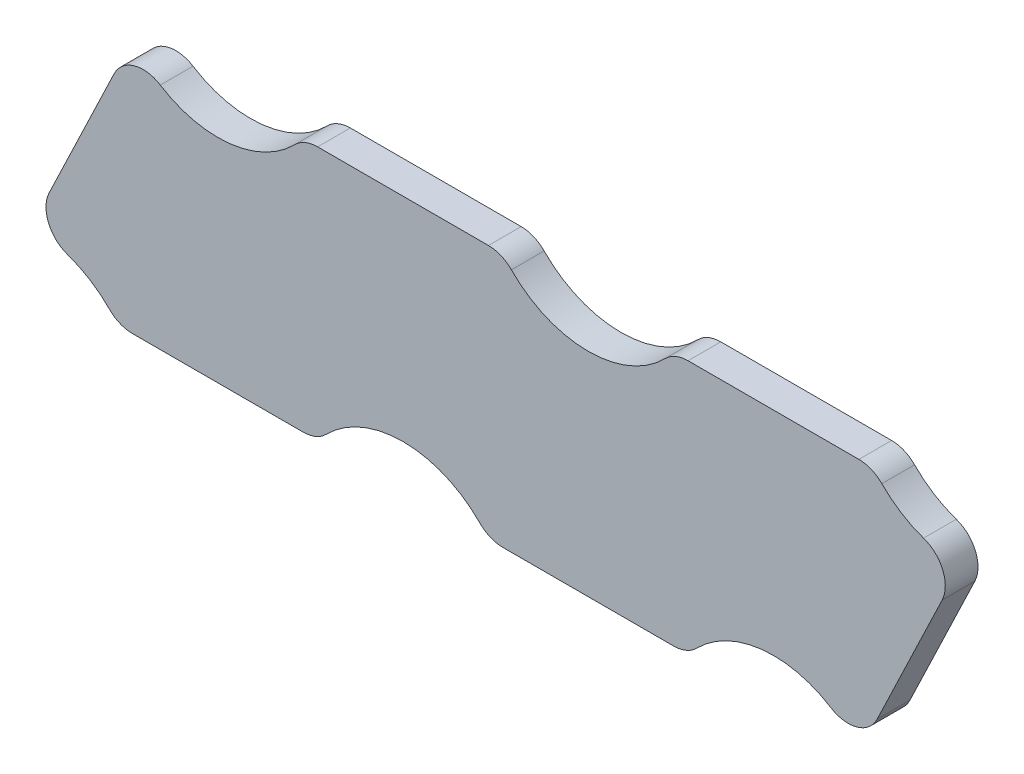
SolidWorks part; units mm, degrees
material "3003-H14"
ref_plane "X-Y Datum" through (0, 0, 0) normal (0, 0, 1) x (1, 0, 0)
ref_plane "X-Z Datum" through (0, 0, 0) normal (0, 1, 0) x (1, 0, 0)
ref_plane "Y-Z Datum" through (0, 0, 0) normal (1, 0, 0) x (0, 0, -1)
sketch "Sketch3" plane through (0, 0, 0) normal (0, 0, 1) x (1, 0, 0)
  line L0 (10.775, 10.775) -> (22.275, 34.775) construction
  line L1 (0, 0) -> (156.4633, 0) construction
  line L2 (0, 0) -> (0, 56.3098) construction
  line L3 (0, 56.3098) -> (156.4633, 56.3098) construction
  line L4 (156.4633, 0) -> (156.4633, 56.3098) construction
  line L5 (33.775, 10.775) -> (45.275, 34.775) construction
  line L6 (56.775, 10.775) -> (68.275, 34.775) construction
  line L7 (16.525, 22.775) -> (62.525, 22.775) construction
  line L8 (33.775, 10.775) -> (22.275, 34.775) construction
  line L9 (45.275, 34.775) -> (56.775, 10.775) construction
  line L10 (10.775, 10.775) -> (33.775, 10.775) construction
  line L11 (56.775, 10.775) -> (33.775, 10.775) construction
  line L12 (22.275, 34.775) -> (45.275, 34.775) construction
  line L13 (68.275, 34.775) -> (45.275, 34.775) construction
  line L14 (22.275, 34.775) -> (22.275, 10.775) construction
  line L15 (45.275, 10.775) -> (45.275, 34.775) construction
  line L16 (33.775, 10.775) -> (33.775, 34.775) construction
  line L17 (56.775, 34.775) -> (56.775, 10.775) construction
  line L18 (13.4804, 9.4786) -> (24.9804, 33.4786)
  line L19 (36.4804, 9.4786) -> (47.9804, 33.4786)
  line L20 (59.4804, 9.4786) -> (70.9804, 33.4786)
  line L21 (8.0696, 12.0714) -> (19.5696, 36.0714)
  line L22 (31.0696, 12.0714) -> (42.5696, 36.0714)
  line L23 (54.0696, 12.0714) -> (65.5696, 36.0714)
  line L24 (17.8152, 18.525) -> (57.1619, 18.525)
  line L25 (21.8881, 27.025) -> (61.2348, 27.025)
  line L26 (16.525, 27.025) -> (62.525, 27.025) construction
  line L27 (16.525, 18.525) -> (62.525, 18.525) construction
  line L28 (16.0692, 14.8813) -> (28.4808, 14.8813)
  line L29 (39.9808, 30.6687) -> (27.5692, 30.6687)
  line L48 (56.775, 10.775) -> (68.275, 10.775) construction
  line L49 (68.275, 10.775) -> (68.275, 34.775) construction
  line L50 (62.9808, 30.6687) -> (50.5692, 30.6687)
  line L51 (39.0692, 14.8813) -> (51.4808, 14.8813)
  circle A0 centre (10.775, 10.775) radius 10.775 construction
  circle A1 centre (33.775, 10.775) radius 10.775 construction
  circle A2 centre (22.275, 34.775) radius 10.775 construction
  circle A3 centre (45.275, 34.775) radius 10.775 construction
  circle A4 centre (68.275, 34.775) radius 10.775 construction
  circle A5 centre (56.775, 10.775) radius 10.775 construction
  circle A6 centre (10.775, 10.775) radius 4.7 construction
  circle A7 centre (33.775, 10.775) radius 4.7 construction
  circle A8 centre (56.775, 10.775) radius 4.7 construction
  circle A9 centre (68.275, 34.775) radius 4.7 construction
  circle A10 centre (45.275, 34.775) radius 4.7 construction
  circle A11 centre (22.275, 34.775) radius 4.7 construction
  circle A12 centre (22.275, 34.775) radius 6.7
  circle A13 centre (10.775, 10.775) radius 6.7
  circle A14 centre (33.775, 10.775) radius 6.7
  circle A15 centre (45.275, 34.775) radius 6.7
  circle A16 centre (68.275, 34.775) radius 6.7
  circle A17 centre (56.775, 10.775) radius 6.7
  circle A18 centre (125.775, 10.775) radius 10.775 construction
  circle A19 centre (102.775, 10.775) radius 10.775 construction
  circle A20 centre (79.775, 10.775) radius 10.775 construction
  circle A21 centre (91.275, 34.775) radius 10.775 construction
  circle A22 centre (114.275, 34.775) radius 10.775 construction
  circle A23 centre (137.275, 34.775) radius 10.775 construction
  dimension "D1" = 21.55
  dimension "D9" = 9.4
  dimension "D2" = 23
  dimension "D3" = 24
  dimension "D4" = 11.5
  dimension "D6" = 23
  dimension "D8" = 23
  dimension "D10" = 3
  dimension "D11" = 3
  dimension "D12" = 4.25
  dimension "D13" = 4.25
  dimension "D14" = 2
  dimension "D5" = 6
  dimension "D7" = 5
extrude "Boss-Extrude1" add sketch "Sketch3" along normal blind 2.032 contours L17 | L17 | L17 | L17 | L49 | A13 L18 A12 L21 | L25 L18 L24 L22 | L25 L22 L24 L19 | L25 L19 L24 L23 | A17 L20 A16 L23 | A14 L19 L24 L22 | A15 L22 L25 L19 | A14 L22 L24 L18 L28 | A12 L18 L25 L22 L29 | A17 L23 L24 L19 L51 | A15 L19 L25 L23 L50 region at (16.525, 22.775, 0) region at (24.1977, 16.8116, 0) region at (28.025, 22.775, 0) region at (31.8523, 28.7384, 0) region at (37.7051, 17.4114, 0) region at (39.525, 22.775, 0) region at (41.3449, 28.1386, 0) region at (47.1977, 16.8116, 0) region at (51.025, 22.775, 0) region at (54.8523, 28.7384, 0) region at (62.525, 22.775, 0)
ref_plane "Plane1" through (68.275, 0, 0) normal (1, 0, 0) x (0, 0, -1)
fillet "Fillet1" radius 2 12 edges at (62.9808, 30.6687, 1.016) (50.5692, 30.6687, 1.016) (39.9808, 30.6687, 1.016) (27.5692, 30.6687, 1.016) (16.0692, 14.8813, 1.016) (28.4808, 14.8813, 1.016) (39.0692, 14.8813, 1.016) (51.4808, 14.8813, 1.016) (68.3917, 28.076, 1.016) (62.0692, 14.8813, 1.016) (10.6583, 17.474, 1.016) (16.9808, 30.6687, 1.016)
